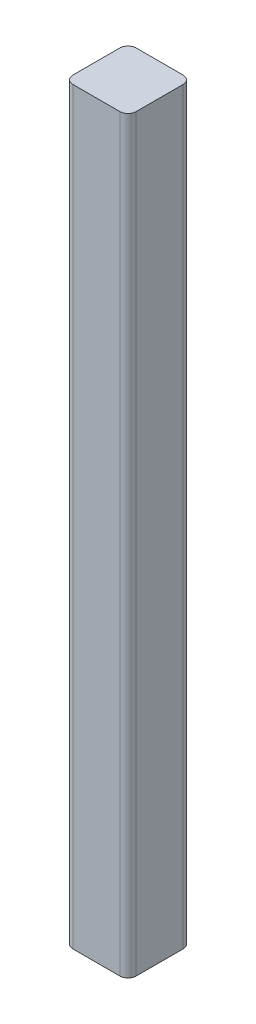
SolidWorks part; units mm, degrees
material "AISI 304"
ref_plane "前视基准面" through (0, 0, 0) normal (0, 0, 1) x (1, 0, 0)
ref_plane "上视基准面" through (0, 0, 0) normal (0, 1, 0) x (1, 0, 0)
ref_plane "右视基准面" through (0, 0, 0) normal (1, 0, 0) x (0, 0, -1)
other "Configuration Table"
sketch "草图1" plane through (0, 0, 0) normal (0, 1, 0) x (1, 0, 0)
  line L5 (-2.605, 3.505) -> (2.605, 3.505)
  line L6 (2.605, -3.505) -> (-2.605, -3.505)
  line L10 (3.505, -2.605) -> (3.505, 2.605)
  line L11 (2.605, 3.505) -> (-2.605, 3.505)
  line L12 (-3.505, -2.605) -> (-3.505, 2.605)
  line L13 (3.2414, -3.2414) -> (-3.2414, 3.2414) construction
  line L14 (3.2414, 3.2414) -> (-3.2414, -3.2414) construction
  line L15 (-3.505, 2.605) -> (-3.505, -2.605)
  line L16 (-2.605, -3.505) -> (2.605, -3.505)
  line L17 (3.505, 2.605) -> (3.505, -2.605)
  arc A4 (-2.605, 3.505) -> (-3.505, 2.605) centre (-2.605, 2.605) ccw
  arc A5 (-3.505, -2.605) -> (-2.605, -3.505) centre (-2.605, -2.605) ccw
  arc A6 (2.605, -3.505) -> (3.505, -2.605) centre (2.605, -2.605) ccw
  arc A7 (3.505, 2.605) -> (2.605, 3.505) centre (2.605, 2.605) ccw
  point P0 (0, 0)
  point P6 (2.605, 3.505)
  point P7 (3.505, 2.605)
  point P8 (-2.605, 3.505)
  point P9 (-3.505, 2.605)
  point P10 (-3.505, -2.605)
  point P11 (-2.605, -3.505)
  point P12 (2.605, -3.505)
  point P13 (3.505, -2.605)
  dimension "D1" = 3.505
  dimension "D2" = 3.505
  dimension "D3" = 0.9
  dimension "D4" = 0.9
  dimension "D5" = 0.9
  dimension "D6" = 0.9
  dimension "D7" = 0.9
  dimension "D8" = 0.9
  dimension "D9" = 0.9
  dimension "D10" = 0.9
  dimension "D11" = 3.505
  dimension "D12" = 3.505
  dimension "D13" = 4.584
  dimension "D14" = 4.584
extrude "凸台-拉伸2" add sketch "草图1" along normal blind 83 contours L12 A4 L5 A7 L10 A6 L6 A5
sketch "草图3" plane through (0, 83, 0) normal (0, 1, 0) x (1, 0, 0)
  line L0 (-3.505, 2.605) -> (-3.505, -2.605)
  line L1 (-2.605, -3.505) -> (2.605, -3.505)
  line L2 (-2.605, 3.505) -> (2.605, 3.505)
  line L3 (3.505, 2.605) -> (3.505, -2.605)
  arc A0 (-3.505, 2.605) -> (-2.605, 3.505) centre (-2.605, 2.605) cw
  arc A1 (2.605, 3.505) -> (3.505, 2.605) centre (2.605, 2.605) cw
  arc A2 (3.505, -2.605) -> (2.605, -3.505) centre (2.605, -2.605) cw
  arc A3 (-2.605, -3.505) -> (-3.505, -2.605) centre (-2.605, -2.605) cw
  circle A4 centre (0, 0) radius 3.556
  point P23 (0, 0)
  dimension "D1" = 7.112
